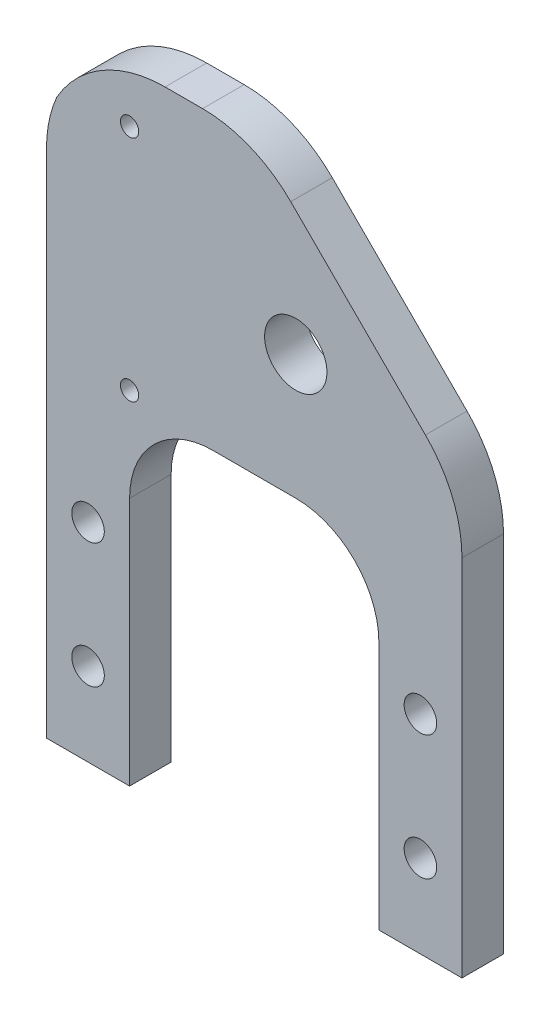
SolidWorks part; units mm, degrees
material "6061-T6 (SS)"
ref_plane "Front Plane" through (0, 0, 0) normal (0, 0, 1) x (1, 0, 0)
ref_plane "Top Plane" through (0, 0, 0) normal (0, 1, 0) x (1, 0, 0)
ref_plane "Right Plane" through (0, 0, 0) normal (1, 0, 0) x (0, 0, -1)
sketch "Sketch1" plane through (0, 0, 0) normal (0, 0, 1) x (1, 0, 0)
  line L1 (0, 0) -> (12.7, 0)
  line L2 (0, 0) -> (0, 82.55)
  line L5 (50.8, 0) -> (63.5, 0)
  line L8 (63.5, 0) -> (63.5, 63.5)
  line L13 (12.7, 0) -> (12.7, 50.8)
  line L14 (12.7, 50.8) -> (50.8, 50.8)
  line L15 (50.8, 50.8) -> (50.8, 0)
  line L17 (6.35, 95.25) -> (0, 82.55)
  line L18 (6.35, 95.25) -> (31.75, 95.25)
  line L19 (31.75, 95.25) -> (63.5, 63.5)
  dimension "D3" = 82.55
  dimension "D1" = 25.4
  dimension "D2" = 95.25
  dimension "D4" = 12.7
  dimension "D5" = 63.5
  dimension "D6" = 50.8
  dimension "D7" = 12.7
  dimension "D8" = 31.75
  dimension "D9" = 63.5
extrude "Boss-Extrude1" add sketch "Sketch1" along normal blind 6.35
sketch "Sketch2" plane through (0, 0, 6.35) normal (0, 0, 1) x (1, 0, 0)
  circle A0 centre (6.35, 12.7) radius 2.4892
  circle A1 centre (6.35, 31.75) radius 2.4892
  circle A2 centre (57.15, 12.7) radius 2.4892
  circle A3 centre (57.15, 31.75) radius 2.4892
  dimension "D1" = 4.9784
  dimension "D2" = 4.9784
  dimension "D3" = 6.35
  dimension "D4" = 12.7
  dimension "D5" = 19.05
  dimension "D6" = 50.8
extrude "Cut-Extrude1" cut sketch "Sketch2" against normal up to next
sketch "Sketch4" plane through (0, 0, 6.35) normal (0, 0, 1) x (1, 0, 0)
  line L0 (63.5, 0) -> (63.5, 63.5) construction
  line L1 (50.8, 0) -> (63.5, 0) construction
  circle A0 centre (12.7, 52.3875) radius 1.397
  circle A1 centre (12.7, 87.3125) radius 1.397
  circle A3 centre (38.1, 69.85) radius 4.7625
  dimension "D1" = 2.794
  dimension "D7" = 9.525
  dimension "D2" = 34.925
  dimension "D3" = 25.4
  dimension "D4" = 69.85
  dimension "D5" = 17.4625
  dimension "D6" = 25.4
extrude "Cut-Extrude3" cut sketch "Sketch4" against normal up to next
fillet "Fillet4" radius 12.7 2 edges at (50.8, 50.8, 3.175) (12.7, 50.8, 3.175)
fillet "Fillet5" radius 19.05 4 edges at (0, 82.55, 3.175) (6.35, 95.25, 3.175) (31.75, 95.25, 3.175) (63.5, 63.5, 3.175)
